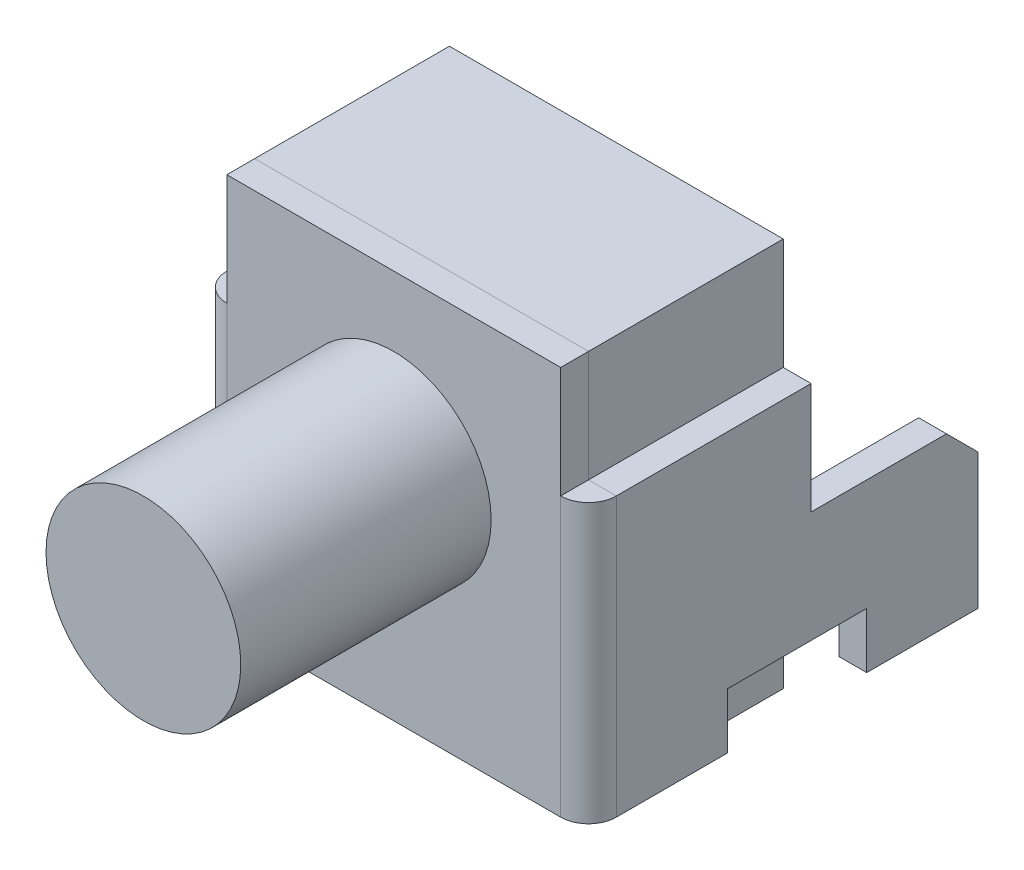
SolidWorks part; units mm, degrees
note: The reader was unsure of these and kept them because the rebuilt part matched: shared geometry of "Эскиз1<3>", "Эскиз1<4>".
ref_plane "Front" through (0, 0, 0) normal (0, 0, 1) x (1, 0, 0)
ref_plane "Top" through (0, 0, 0) normal (0, 1, 0) x (1, 0, 0)
ref_plane "Right" through (0, 0, 0) normal (1, 0, 0) x (0, 0, -1)
sketch "Эскиз1" plane through (0, 0, 0) normal (1, 0, 0) x (0, 0, -1)
  line L0 (0, 0) -> (0, 7)
  line L1 (0, 7) -> (3.5, 7)
  line L2 (3.5, 7) -> (3.5, 3)
  line L3 (3.5, 3) -> (5.9343, 3)
  line L4 (5.9343, 3) -> (6.5, 2.4343)
  line L5 (6.5, 2.4343) -> (6.5, 0)
  line L6 (6.5, 0) -> (4.5, 0)
  line L7 (4.5, 0) -> (4.5, 1)
  line L8 (4.5, 1) -> (2, 1)
  line L9 (2, 1) -> (2, 0)
  line L10 (2, 0) -> (0, 0)
  line L11 (0, 5) -> (3.5, 5)
  line L12 (3.5, 3) -> (3.5, 0)
  line L13 (3.5, 0) -> (2, 0)
  dimension "D1" = 3.5
  dimension "D2" = 7
  dimension "D3" = 45
  dimension "D4" = 3
  dimension "D5" = 1
  dimension "D6" = 2
  dimension "D7" = 6.5
  dimension "D8" = 0.8
  dimension "D9" = 2
extrude "Бобышка-Вытянуть1" add sketch "Эскиз1" along normal blind 0.5 contours L11 L0 L10 L9 L8 L7 L6 L5 L4 L3 L2 | L3 L12 L8 L7 L6 L5 L4
extrude "Бобышка-Вытянуть2" add sketch "Эскиз1<3>" against normal blind 6 separate body contours L13 L12 L8 L9 | L12 L2 L11 L0 L10 L9 L8 | L0 L11 L2 L1
sketch "Эскиз1<3>" plane through (0, 0, 0) normal (1, 0, 0) x (0, 0, -1) same geometry as "Эскиз1"
extrude "Бобышка-Вытянуть3" add sketch "Эскиз1<4>" against normal blind 0.5 from surface at -6 contours L3 L12 L8 L7 L6 L5 L4 | L12 L2 L11 L0 L10 L9 L8 starting at face at (-6, 3.5, -1.75)
sketch "Эскиз1<4>" plane through (0, 0, 0) normal (1, 0, 0) x (0, 0, -1) same geometry as "Эскиз1"
sketch "Эскиз2" plane through (0, 0, 0) normal (0, 0, 1) x (1, 0, 0)
  line L1 (0, 7) -> (-6, 7) construction
  line L2 (0, 7) -> (0, 1) construction
  line L3 (0, 1) -> (-6, 1) construction
  line L4 (-6, 7) -> (-6, 1) construction
  line L5 (-3, 1) -> (-3, 7) construction
  line L6 (0, 4) -> (-6, 4) construction
  circle A0 centre (-3, 4) radius 1.75
  point P236 (-3, 4)
  dimension "D1" = 3.5
extrude "Бобышка-Вытянуть4" add sketch "Эскиз2" along normal blind 5 contours A0
sketch "Эскиз3" plane through (0, 0, 0) normal (0, 0, 1) x (1, 0, 0)
  line L4 (0, 0) -> (0, 7)
  line L5 (0, 7) -> (-6, 7)
  line L6 (-6, 7) -> (-6, 0)
  line L7 (-6, 0) -> (0, 0)
  line L8 (0, 0) -> (0, 7)
  line L9 (0, 7) -> (-6, 7)
  line L10 (-6, 7) -> (-6, 0)
  line L11 (-6, 0) -> (0, 0)
  circle A0 centre (-3, 4) radius 1.75 construction
  circle A1 centre (-3, 4) radius 1.75
  dimension "D1" = 0
extrude "Бобышка-Вытянуть5" add sketch "Эскиз3" along normal blind 0.5 separate body
sketch "Эскиз4" plane through (0, 5, 0) normal (0, 1, 0) x (1, 0, 0)
  line L0 (-6.5, 0) -> (-6, -0.5)
sketch "Эскиз5" plane through (0, 0, 0) normal (0, 0, 1) x (1, 0, 0)
  line L4 (-6, 0) -> (-6, 5)
  line L5 (-6, 5) -> (-6.5, 5)
  line L6 (-6.5, 5) -> (-6.5, 0)
  line L7 (-6.5, 0) -> (-6, 0)
  line L8 (-6, 0) -> (-6, 5)
  line L9 (-6, 5) -> (-6.5, 5)
  line L10 (-6.5, 5) -> (-6.5, 0)
  line L11 (-6.5, 0) -> (-6, 0)
  dimension "D1" = 0
revolve "Повернуть1" add sketch "Эскиз5" angle 90 about L8
sketch "Эскиз6" plane through (0, 0, 0) normal (0, 0, 1) x (1, 0, 0)
  line L4 (0, 5) -> (0, 0)
  line L5 (0, 0) -> (0.5, 0)
  line L6 (0.5, 0) -> (0.5, 5)
  line L7 (0.5, 5) -> (0, 5)
  line L8 (0, 5) -> (0, 0)
  line L9 (0, 0) -> (0.5, 0)
  line L10 (0.5, 0) -> (0.5, 5)
  line L11 (0.5, 5) -> (0, 5)
  dimension "D1" = 0
revolve "Повернуть2" add sketch "Эскиз6" angle 90 about L8
